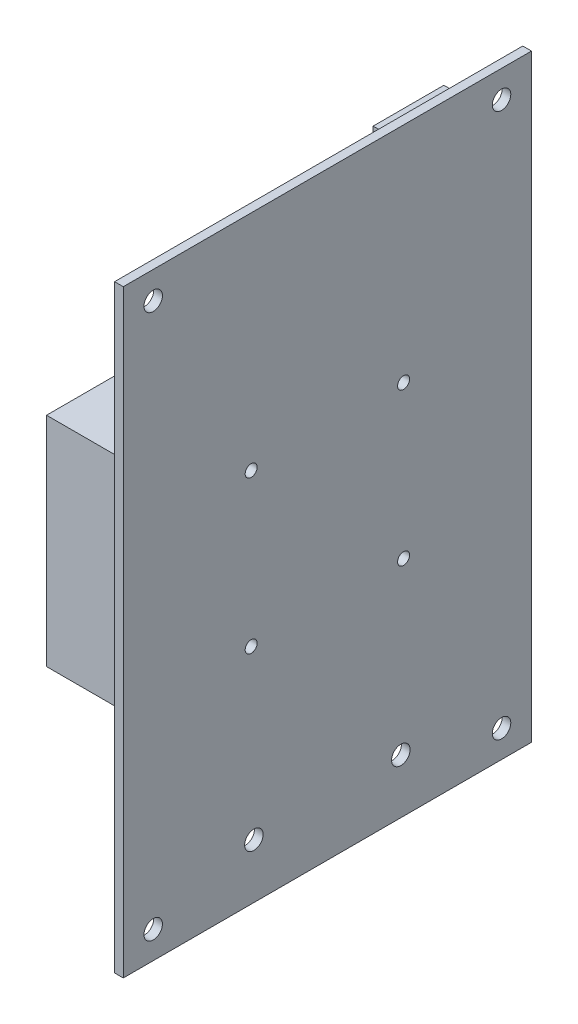
SolidWorks part; units mm, degrees
ref_plane "Front Plane" through (0, 0, 0) normal (0, 0, 1) x (1, 0, 0)
ref_plane "Top Plane" through (0, 0, 0) normal (0, 1, 0) x (1, 0, 0)
ref_plane "Right Plane" through (0, 0, 0) normal (1, 0, 0) x (0, 0, -1)
sketch "Board Sketch" plane through (0, 0, 0) normal (1, 0, 0) x (0, 0, -1)
  line L0 (37.5, -55) -> (37.5, 55)
  line L1 (37.5, 55) -> (-37.5, 55)
  line L2 (-37.5, 55) -> (-37.5, -55)
  line L3 (-37.5, -55) -> (37.5, -55)
  circle A0 centre (32, -50) radius 1.7
  circle A1 centre (-32, -50) radius 1.7
  circle A2 centre (32, 50) radius 1.7
  circle A3 centre (-32, 50) radius 1.7
  circle A4 centre (13.5, -45) radius 1.7
  circle A5 centre (-13.5, -45) radius 1.7
  circle A6 centre (14, -14) radius 1.1
  circle A7 centre (-14, -14) radius 1.1
  circle A8 centre (14, 14) radius 1.1
  circle A9 centre (-14, 14) radius 1.1
extrude "Board" add sketch "Board Sketch" against normal blind 1.6 from offset 30 offset against normal yes
ref_axis "Engine Axis" through (-29.17, 0, 0) along (-1, 0, 0)
sketch "Teensy 4.1 Sketch" plane through (0, 0, 0) normal (1, 0, 0) x (0, 0, -1)
  line L0 (37, -30.5) -> (37, 30.5)
  line L1 (37, 30.5) -> (19, 30.5)
  line L2 (19, 30.5) -> (19, -30.5)
  line L3 (19, -30.5) -> (37, -30.5)
extrude "Teensy 4.1" add sketch "Teensy 4.1 Sketch" against normal blind 5 from offset 31.6 offset against normal yes
sketch "Barometer BMP388 board [est] Sketch" plane through (0, 0, 0) normal (1, 0, 0) x (0, 0, -1)
  line L0 (26, 35) -> (26, 53)
  line L1 (26, 53) -> (13, 53)
  line L2 (13, 53) -> (13, 35)
  line L3 (13, 35) -> (26, 35)
extrude "Barometer BMP388 board [est]" add sketch "Barometer BMP388 board [est] Sketch" against normal blind 3 from offset 31.6 offset against normal yes
sketch "Vent backup Sketch" plane through (0, 0, 0) normal (1, 0, 0) x (0, 0, -1)
  line L0 (-20, -15) -> (-20, 25)
  line L1 (-20, 25) -> (-35, 25)
  line L2 (-35, 25) -> (-35, -15)
  line L3 (-35, -15) -> (-20, -15)
extrude "Vent backup" add sketch "Vent backup Sketch" against normal blind 15 from offset 31.6 offset against normal yes
